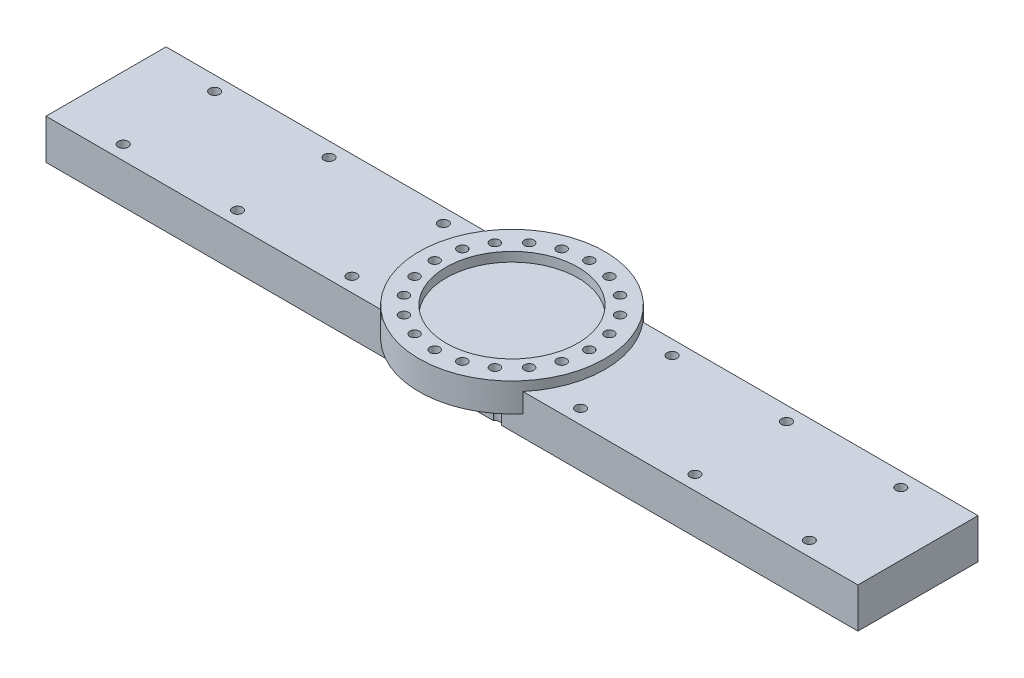
SolidWorks part; units mm, degrees
ref_plane "Front Plane" through (0, 0, 0) normal (0, 0, 1) x (1, 0, 0)
ref_plane "Top Plane" through (0, 0, 0) normal (0, 1, 0) x (1, 0, 0)
ref_plane "Right Plane" through (0, 0, 0) normal (1, 0, 0) x (0, 0, -1)
sketch "Sketch1" plane through (0, 0, 0) normal (0, 1, 0) x (1, 0, 0)
  line L0 (15.8996, 21.8839) -> (0, 0) construction
  line L1 (0, 0) -> (27.05, 0) construction
  circle A0 centre (0, 0) radius 27.05 construction
  circle A1 centre (15.8996, 21.8839) radius 1.675
  circle A2 centre (0, 0) radius 32.5
  circle A3 centre (21.8839, 15.8996) radius 1.675
  circle A4 centre (25.7261, 8.3589) radius 1.675
  circle A5 centre (27.05, 0) radius 1.675
  circle A6 centre (25.7261, -8.3589) radius 1.675
  circle A7 centre (21.8839, -15.8996) radius 1.675
  circle A8 centre (15.8996, -21.8839) radius 1.675
  circle A9 centre (8.3589, -25.7261) radius 1.675
  circle A10 centre (0, -27.05) radius 1.675
  circle A11 centre (-8.3589, -25.7261) radius 1.675
  circle A12 centre (-15.8996, -21.8839) radius 1.675
  circle A13 centre (-21.8839, -15.8996) radius 1.675
  circle A14 centre (-25.7261, -8.3589) radius 1.675
  circle A15 centre (-27.05, 0) radius 1.675
  circle A16 centre (-25.7261, 8.3589) radius 1.675
  circle A17 centre (-21.8839, 15.8996) radius 1.675
  circle A18 centre (-15.8996, 21.8839) radius 1.675
  circle A19 centre (-8.3589, 25.7261) radius 1.675
  circle A20 centre (0, 27.05) radius 1.675
  circle A21 centre (8.3589, 25.7261) radius 1.675
  point P49 (0, 0)
  dimension "D2" = 3.35
  dimension "D3" = 54.1
  dimension "D4" = 65
  dimension "D1" = 54
  dimension "D5" = 20
extrude "Boss-Extrude1" add sketch "Sketch1" along normal blind 10
sketch "Sketch2" plane through (0, 10, 0) normal (0, 1, 0) x (1, 0, 0)
  circle A0 centre (0, 0) radius 23.05
  dimension "D1" = 46.1
extrude "Cut-Extrude1" cut sketch "Sketch2" against normal blind 3.25
sketch "Sketch3" plane through (0, 0, 0) normal (0, -1, 0) x (1, 0, 0)
  line L0 (-142, 21) -> (142, 21)
  line L1 (-142, 21) -> (-142, -21)
  line L2 (-142, -21) -> (142, -21)
  line L3 (142, 21) -> (142, -21)
  line L4 (-120, 16) -> (120, 16) construction
  line L5 (-120, 16) -> (-120, -16) construction
  line L6 (-120, -16) -> (120, -16) construction
  line L7 (120, 16) -> (120, -16) construction
  circle A0 centre (-120, 16) radius 1.75
  circle A1 centre (-80, 16) radius 1.75
  circle A2 centre (-40, 16) radius 1.75
  circle A3 centre (0, 16) radius 1.75
  circle A4 centre (40, 16) radius 1.75
  circle A5 centre (80, 16) radius 1.75
  circle A6 centre (120, 16) radius 1.75
  circle A7 centre (120, -16) radius 1.75
  circle A8 centre (80, -16) radius 1.75
  circle A9 centre (40, -16) radius 1.75
  circle A10 centre (0, -16) radius 1.75
  circle A11 centre (-40, -16) radius 1.75
  circle A12 centre (-80, -16) radius 1.75
  circle A13 centre (-120, -16) radius 1.75
  point P35 (-120, 0)
  point P36 (-142, 0)
  point P37 (0, 0)
  point P38 (0, 0)
  point P39 (0, 0)
  point P40 (0, 0)
  point P41 (0, 0)
  point P42 (0, 0)
  point P43 (0, 0)
  point P44 (0, 0)
  point P45 (0, 0)
  point P46 (0, 0)
  point P47 (0, 0)
  point P48 (0, 0)
  point P49 (0, 0)
  point P50 (0, 0)
  point P51 (0, 0)
  point P53 (0, 0)
  point P54 (0, 0)
  point P55 (0, 0)
  point P56 (0, 0)
  point P57 (0, -21)
  dimension "D10" = 3.5
  dimension "D1" = 42
  dimension "D2" = 284
  dimension "D3" = 40
  dimension "D4" = 40
  dimension "D5" = 40
  dimension "D6" = 40
  dimension "D7" = 40
  dimension "D8" = 40
  dimension "D9" = 32
extrude "Boss-Extrude2" add sketch "Sketch3" against normal blind 6.75 and the other way blind 7.25
extrude "Cut-Extrude2" cut sketch "Sketch1<2>" against normal through all and the other way through all contours A18 | A20 | A21 | A1 | A8 | A9 | A10 | A11 | A19 | A3 | A4 | A5 | A6 | A7 | A12 | A13 | A14 | A15 | A16 | A17 region at (15.8996, 0, -21.8839) region at (15.8996, 0, 21.8839) region at (8.3589, 0, 25.7261) region at (0, 0, 27.05) region at (-8.3589, 0, 25.7261) region at (-15.8996, 0, -21.8839) region at (0, 0, -27.05) region at (8.3589, 0, -25.7261)
sketch "Sketch1<2>" plane through (0, 0, 0) normal (0, 1, 0) x (1, 0, 0) same geometry as "Sketch1"
